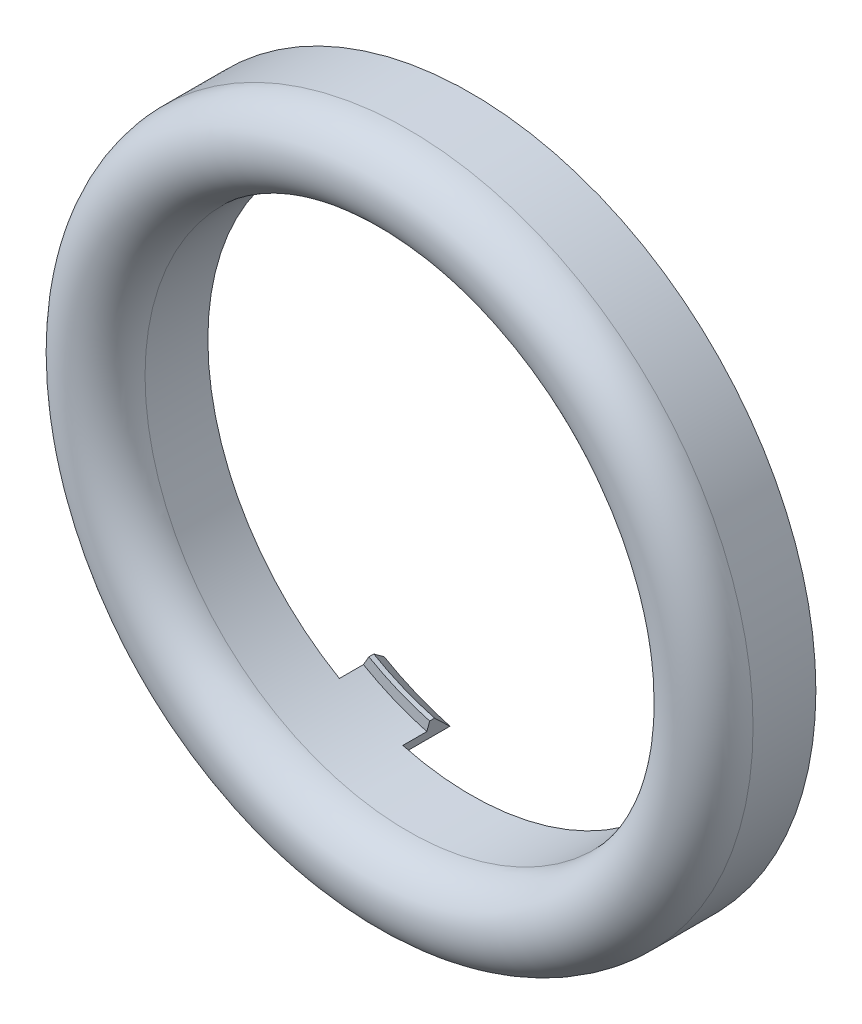
SolidWorks part; units mm, degrees
other "Diffuser" parameters "Inside Diameter"=48.15, "Outside Diameter"=63.15
ref_plane "Top" through (0, 0, 0) normal (0, 0, 1) x (1, 0, 0)
ref_plane "Front" through (0, 0, 0) normal (0, 1, 0) x (1, 0, 0)
ref_plane "Right" through (0, 0, 0) normal (1, 0, 0) x (0, 0, -1)
sketch "Diffuser" plane through (0, 0, 0) normal (0, 1, 0) x (-1, 0, 0)
  line L0 (31.575, 0) -> (31.575, 5.75)
  line L1 (31.575, 0) -> (24.075, 0)
  line L2 (24.075, 0) -> (24.075, 5.75)
  line L3 (31.575, 9.5) -> (24.075, 9.5) construction
  line L4 (0, 0) -> (0, 10) construction
  arc A0 (31.575, 5.75) -> (24.075, 5.75) centre (27.825, 5.75) ccw
  dimension "D2" = 9.5
  dimension "D3" = 10
revolve "Diffuser Revolve" add sketch "Diffuser" angle 360 about L4
sketch "Tabs" plane through (36.2137, 0, -46.3233) normal (0, 1, 0) x (-1, 0, 0)
  line L0 (12.1387, 44.1233) -> (12.1387, 46.3233)
  line L1 (36.2137, 46.3233) -> (36.2137, 51.3233) construction
  line L2 (12.1387, 44.1233) -> (13.1387, 44.1233)
  line L3 (13.1387, 44.1233) -> (13.1387, 43.6733)
  line L4 (13.1387, 43.6733) -> (11.2387, 41.7733)
  line L5 (11.2387, 41.7733) -> (11.2387, 46.3233)
  line L6 (11.2387, 46.3233) -> (12.1387, 46.3233)
  dimension "D1" = 5
  dimension "D2" = 0.9
  dimension "D3" = 4.55
  dimension "D4" = 2.2
  dimension "D5" = 45
  dimension "D6" = 1
  dimension "D7" = 48.15
revolve "Tab Revolve" add sketch "Tabs" angle 15 about L1
pattern_circular "Tab Pattern" count 3 over 360 about axis through (0, 0, 0) along (0, 0, 1) of bodies 102
combine bodies "Ring and Tabs Combine" operation type add bodies to combine 101 104 103 102
